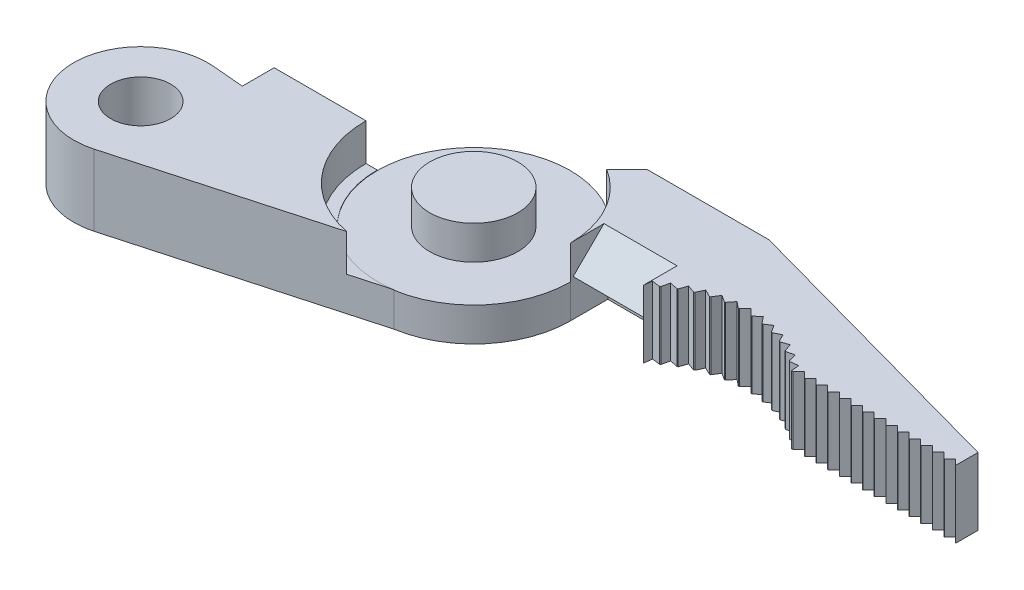
SolidWorks part; units mm, degrees
material "Plain Carbon Steel"
ref_plane "Front Plane" through (0, 0, 0) normal (0, 0, 1) x (1, 0, 0)
ref_plane "Top Plane" through (0, 0, 0) normal (0, 1, 0) x (1, 0, 0)
ref_plane "Right Plane" through (0, 0, 0) normal (1, 0, 0) x (0, 0, -1)
sketch "Sketch1" plane through (0, 0, 0) normal (0, 1, 0) x (1, 0, 0)
  circle A0 centre (0, 0) radius 6.5405
  circle A1 centre (0, 0) radius 2.9845
  dimension "D1" = 13.081
  dimension "D2" = 5.969
extrude "Boss-Extrude1" add sketch "Sketch1" along normal blind 4.826
sketch "Sketch2" plane through (0, 0, 0) normal (0, 1, 0) x (1, 0, 0)
  line L0 (-6.5405, 0) -> (-13.5255, 0)
  line L1 (-13.5255, 0) -> (-13.5255, -2.159)
  line L2 (-15.6763, -1.9708) -> (-13.5255, -2.159)
  line L3 (1.0584, -6.4543) -> (-14.8567, -10.8736)
  circle A1 centre (-16.0722, -6.4964) radius 2.032
  circle A2 centre (0, 0) radius 2.9845 construction
  arc A3 (-15.6763, -1.9708) -> (-14.8567, -10.8736) centre (-16.0722, -6.4964) ccw
  arc A4 (-6.5405, 0) -> (1.0584, -6.4543) centre (0, 0) ccw
  dimension "D1" = 4.064
  dimension "D6" = 17.3355
  dimension "D7" = 1.0584
  dimension "D3" = 4.5429
  dimension "D4" = 6.5405
  dimension "D2" = 6.985
  dimension "D5" = 85
extrude "Boss-Extrude2" add sketch "Sketch2" along normal up to surface (4.826 mm away) up to face at (0, 4.826, 6.5405)
hole_wizard "#42 (0.0935) Diameter Hole1" positions "Sketch6" profile "Sketch7" hole size "#42" standard "ANSI Inch"
sketch "Sketch6" plane through (0, 0, 0) normal (0, 0, -1) x (-1, 0, 0)
  line L0 (13.5255, 4.826) -> (13.5255, 0) construction
  line L1 (6.5405, 0) -> (13.5255, 0) construction
  point P0 (10.033, 2.413)
  dimension "D1" = 3.4925
  dimension "D2" = 2.413
sketch "Sketch7" plane through (-10.033, 2.413, 0) normal (1, 0, 0) x (0, 1, 0)
  line L0 (0, 0) -> (0, 2.7455)
  line L1 (0, 2.7455) -> (1.1874, 2.032)
  line L2 (1.1874, 2.032) -> (1.1874, 0)
  line L5 (1.1874, 0) -> (0, 0)
  line L10 (0, 2.7455) -> (-1.1875, 2.032) construction
  line L11 (0, -6.35) -> (0, 107.95) construction
  dimension "Hole Dia." = 2.3749
  dimension "Hole Depth" = 2.032
  dimension "Drill Angle" = 118
sketch "Sketch8" plane through (0, 0, 0) normal (0, 1, 0) x (1, 0, 0)
  line L0 (13.081, 6.9215) -> (32.639, 1.524)
  line L1 (32.639, 1.524) -> (32.639, 0)
  line L2 (32.639, 0) -> (21.5265, 0)
  line L3 (13.081, 6.9215) -> (4.826, 6.9215)
  line L4 (4.826, 6.9215) -> (3.4568, 5.5523)
  line L5 (6.5405, 0) -> (11.4935, 0)
  arc A2 (1.0584, -6.4543) -> (-6.5405, 0) centre (0, 0) ccw construction
  arc A4 (21.5265, 0) -> (11.4935, 0) centre (16.51, -5.7358) ccw
  arc A5 (6.5405, 0) -> (3.4568, 5.5523) centre (0, 0) ccw
  dimension "D1" = 0.381
  dimension "D8" = 7.62
  dimension "D2" = 1.524
  dimension "D3" = 8.255
  dimension "D4" = 32.639
  dimension "D5" = 225
  dimension "D6" = 11.1125
  dimension "D7" = 4.953
  dimension "D9" = 4.826
extrude "Boss-Extrude3" add sketch "Sketch8" along normal up to surface (4.826 mm away) up to face at (-10.2367, 4.826, 2.2894)
sketch "Sketch9" plane through (0, 4.826, 0) normal (0, 1, 0) x (1, 0, 0)
  line L10 (-7.3025, 0) -> (-6.5405, 0)
  line L11 (-1.463, -7.1544) -> (1.0584, -6.4543)
  line L12 (-14.8567, -10.8736) -> (1.0584, -6.4543) construction
  line L32 (33.401, -0.762) -> (33.401, 2.1048)
  arc A4 (-7.3025, 0) -> (-1.463, -7.1544) centre (0, 0) ccw
  arc A5 (-6.5405, 0) -> (1.0584, -6.4543) centre (0, 0) ccw
  arc A6 (3.4568, 5.5523) -> (-6.5405, 0) centre (0, 0) ccw construction
  arc A7 (1.0584, -6.4543) -> (6.5405, 0) centre (0, 0) ccw construction
  line M26 (-6.5405, 0) -> (-13.5255, 0)
  line M30 (-14.8567, -10.8736) -> (1.0584, -6.4543)
  dimension "D1" = 7.3025
  dimension "D2" = 6.5405
  dimension "D3" = 2.6168
extrude "Cut-Extrude1" cut sketch "Sketch9" against normal blind 2.5082 contours A5 A4 M26 M30 region at (-6.9215, 4.826, 0.11)
sketch "Sketch10" plane through (0, 4.826, 0) normal (0, 1, 0) x (1, 0, 0)
  line L0 (32.639, 0) -> (32.258, 0.381)
  line L1 (32.258, 0.381) -> (31.877, 0)
  line L3 (21.5265, 0) -> (32.639, 0) construction
  line L4 (31.877, 0) -> (32.639, 0)
  dimension "D1" = 0.381
extrude "Cut-Extrude2" cut sketch "Sketch10" against normal through all
pattern_linear "LPattern1" count 14 spacing 0.7874 along (-1, 0, 0) of "Cut-Extrude2"
sketch "Sketch11" plane through (0, 4.826, 0) normal (0, 1, 0) x (1, 0, 0)
  line L0 (21.5265, 0) -> (21.4646, 0.5466)
  line L1 (21.4646, 0.5466) -> (20.9187, 0.4794)
  arc A0 (21.5265, 0) -> (11.4935, 0) centre (16.51, -5.7358) ccw construction
  arc A1 (21.5265, 0) -> (20.9187, 0.4794) centre (16.51, -5.7358) ccw
  dimension "D1" = 8.001
extrude "Cut-Extrude3" cut sketch "Sketch11" against normal through all
pattern_circular "CirPattern1" count 13 over 76.5 about axis through (16.51, 4.826, 5.7358) along (0, -1, 0) of "Cut-Extrude3" reverse direction yes
sketch "Sketch13" plane through (0, 4.826, 0) normal (0, 1, 0) x (1, 0, 0)
  line L0 (11.4935, 0) -> (11.4935, 2.54)
  line L1 (11.4935, 2.54) -> (6.5405, 2.54)
  line L2 (6.5405, 2.54) -> (6.5405, 0)
  line L3 (6.5405, 0) -> (11.4935, 0)
  dimension "D1" = 2.54
extrude "Cut-Extrude5" cut sketch "Sketch13" against normal blind 2.5082
sketch "Sketch14" plane through (6.5405, 0, 0) normal (1, 0, 0) x (0, 0, -1)
  line L0 (0, 2.3178) -> (2.54, 4.826)
  line L1 (2.54, 4.826) -> (2.54, 2.3177)
  line L2 (2.54, 2.3177) -> (2.54, 4.826) construction
  line L3 (2.54, 2.3177) -> (0, 2.3178) construction
  line L4 (2.54, 2.3177) -> (0, 2.3178)
extrude "Boss-Extrude4" add sketch "Sketch14" along normal up to next
sketch "Sketch15" plane through (0, 0, 0) normal (0, -1, 0) x (1, 0, 0)
  line L0 (6.5405, 0) -> (6.5405, -2.54)
  line L1 (6.5405, 0) -> (11.4935, 0) construction
  line L2 (6.5405, -2.54) -> (11.4935, -2.54)
  line L3 (11.4935, -2.54) -> (11.4935, 0)
  line L4 (11.4935, 0) -> (6.5405, 0)
  arc A0 (6.5405, 0) -> (1.0584, 6.4543) centre (0, 0) ccw construction
  dimension "D1" = 2.54
extrude "Cut-Extrude6" cut sketch "Sketch15" against normal blind 2.5082
sketch "Sketch16" plane through (0, 4.826, 0) normal (0, 1, 0) x (1, 0, 0)
  circle A0 centre (0, 0) radius 6.5405
extrude "Cut-Extrude7" cut sketch "Sketch16" against normal blind 2.54
sketch "Sketch18" plane through (0, 0, 0) normal (0, 1, 0) x (1, 0, 0)
  circle A0 centre (0, 0) radius 2.9845
  dimension "D1" = 5.969
extrude "Boss-Extrude5" add sketch "Sketch18" along normal blind 4.572
sketch "Sketch19" plane through (0, 4.826, 0) normal (0, 1, 0) x (1, 0, 0)
  line L76 (6.5405, 0) -> (6.5405, 2.54)
  line L77 (6.5405, 2.54) -> (11.4935, 2.54)
  line L78 (11.4935, 2.54) -> (11.4935, 0)
  line L79 (11.4935, 0) -> (11.4958, 0.002)
  line L80 (11.4958, 0.002) -> (11.5579, 0.5485)
  line L81 (11.5579, 0.5485) -> (12.1038, 0.4811)
  line L82 (12.1639, 0.5233) -> (12.2863, 1.0595)
  line L83 (12.2863, 1.0595) -> (12.8213, 0.9319)
  line L84 (12.8857, 0.9671) -> (13.0669, 1.4865)
  line L85 (13.0669, 1.4865) -> (13.5845, 1.3003)
  line L86 (13.6524, 1.3281) -> (13.8901, 1.8241)
  line L87 (13.8901, 1.8241) -> (14.3838, 1.5816)
  line L88 (14.4544, 1.6017) -> (14.7457, 2.0683)
  line L89 (14.7457, 2.0683) -> (15.2095, 1.7724)
  line L90 (15.2818, 1.7846) -> (15.6232, 2.2159)
  line L91 (15.6232, 2.2159) -> (16.0512, 1.8704)
  line L92 (16.1244, 1.8745) -> (16.5116, 2.2652)
  line L93 (16.5116, 2.2652) -> (16.8986, 1.8743)
  line L94 (16.9718, 1.8702) -> (17.4, 2.2156)
  line L95 (17.4, 2.2156) -> (17.7411, 1.7841)
  line L96 (17.8135, 1.7719) -> (18.2773, 2.0676)
  line L97 (18.2773, 2.0676) -> (18.5685, 1.6009)
  line L98 (18.6391, 1.5807) -> (19.1329, 1.8231)
  line L99 (19.1329, 1.8231) -> (19.3704, 1.327)
  line L100 (19.4383, 1.2991) -> (19.9559, 1.4851)
  line L101 (19.9559, 1.4851) -> (20.1369, 0.9657)
  line L102 (20.2013, 0.9305) -> (20.7364, 1.0579)
  line L103 (20.7364, 1.0579) -> (20.8586, 0.5215)
  line L104 (20.9187, 0.4794) -> (21.4646, 0.5466)
  line L105 (21.4646, 0.5466) -> (21.5265, 0)
  line L106 (21.5265, 0) -> (21.6408, 0)
  line L107 (21.6408, 0) -> (22.0218, 0.381)
  line L108 (22.0218, 0.381) -> (22.4028, 0)
  line L109 (22.4028, 0) -> (22.4282, 0)
  line L110 (22.4282, 0) -> (22.8092, 0.381)
  line L111 (22.8092, 0.381) -> (23.1902, 0)
  line L112 (23.1902, 0) -> (23.2156, 0)
  line L113 (23.2156, 0) -> (23.5966, 0.381)
  line L114 (23.5966, 0.381) -> (23.9776, 0)
  line L115 (23.9776, 0) -> (24.003, 0)
  line L116 (24.003, 0) -> (24.384, 0.381)
  line L117 (24.384, 0.381) -> (24.765, 0)
  line L118 (24.765, 0) -> (24.7904, 0)
  line L119 (24.7904, 0) -> (25.1714, 0.381)
  line L120 (25.1714, 0.381) -> (25.5524, 0)
  line L121 (25.5524, 0) -> (25.5778, 0)
  line L122 (25.5778, 0) -> (25.9588, 0.381)
  line L123 (25.9588, 0.381) -> (26.3398, 0)
  line L124 (26.3398, 0) -> (26.3652, 0)
  line L125 (26.3652, 0) -> (26.7462, 0.381)
  line L126 (26.7462, 0.381) -> (27.1272, 0)
  line L127 (27.1272, 0) -> (27.1526, 0)
  line L128 (27.1526, 0) -> (27.5336, 0.381)
  line L129 (27.5336, 0.381) -> (27.9146, 0)
  line L130 (27.9146, 0) -> (27.94, 0)
  line L131 (27.94, 0) -> (28.321, 0.381)
  line L132 (28.321, 0.381) -> (28.702, 0)
  line L133 (28.702, 0) -> (28.7274, 0)
  line L134 (28.7274, 0) -> (29.1084, 0.381)
  line L135 (29.1084, 0.381) -> (29.4894, 0)
  line L136 (29.4894, 0) -> (29.5148, 0)
  line L137 (29.5148, 0) -> (29.8958, 0.381)
  line L138 (29.8958, 0.381) -> (30.2768, 0)
  line L139 (30.2768, 0) -> (30.3022, 0)
  line L140 (30.3022, 0) -> (30.6832, 0.381)
  line L141 (30.6832, 0.381) -> (31.0642, 0)
  line L142 (31.0642, 0) -> (31.0896, 0)
  line L143 (31.0896, 0) -> (31.4706, 0.381)
  line L144 (31.4706, 0.381) -> (31.8516, 0)
  line L145 (31.8516, 0) -> (31.877, 0)
  line L146 (31.877, 0) -> (32.258, 0.381)
  line L147 (32.258, 0.381) -> (32.639, 0)
  line L148 (32.639, 0) -> (32.639, 1.524)
  line L149 (32.639, 1.524) -> (13.081, 6.9215)
  line L150 (13.081, 6.9215) -> (4.826, 6.9215)
  line L151 (4.826, 6.9215) -> (3.4568, 5.5523)
  line L152 (6.5405, 0) -> (6.5405, 2.54)
  line L153 (6.5405, 2.54) -> (11.4935, 2.54)
  line L154 (11.4935, 2.54) -> (11.4935, 0)
  line L155 (11.4935, 0) -> (11.4958, 0.002)
  line L156 (11.4958, 0.002) -> (11.5579, 0.5485)
  line L157 (11.5579, 0.5485) -> (12.1038, 0.4811)
  line L158 (12.1639, 0.5233) -> (12.2863, 1.0595)
  line L159 (12.2863, 1.0595) -> (12.8213, 0.9319)
  line L160 (12.8857, 0.9671) -> (13.0669, 1.4865)
  line L161 (13.0669, 1.4865) -> (13.5845, 1.3003)
  line L162 (13.6524, 1.3281) -> (13.8901, 1.8241)
  line L163 (13.8901, 1.8241) -> (14.3838, 1.5816)
  line L164 (14.4544, 1.6017) -> (14.7457, 2.0683)
  line L165 (14.7457, 2.0683) -> (15.2095, 1.7724)
  line L166 (15.2818, 1.7846) -> (15.6232, 2.2159)
  line L167 (15.6232, 2.2159) -> (16.0512, 1.8704)
  line L168 (16.1244, 1.8745) -> (16.5116, 2.2652)
  line L169 (16.5116, 2.2652) -> (16.8986, 1.8743)
  line L170 (16.9718, 1.8702) -> (17.4, 2.2156)
  line L171 (17.4, 2.2156) -> (17.7411, 1.7841)
  line L172 (17.8135, 1.7719) -> (18.2773, 2.0676)
  line L173 (18.2773, 2.0676) -> (18.5685, 1.6009)
  line L174 (18.6391, 1.5807) -> (19.1329, 1.8231)
  line L175 (19.1329, 1.8231) -> (19.3704, 1.327)
  line L176 (19.4383, 1.2991) -> (19.9559, 1.4851)
  line L177 (19.9559, 1.4851) -> (20.1369, 0.9657)
  line L178 (20.2013, 0.9305) -> (20.7364, 1.0579)
  line L179 (20.7364, 1.0579) -> (20.8586, 0.5215)
  line L180 (20.9187, 0.4794) -> (21.4646, 0.5466)
  line L181 (21.4646, 0.5466) -> (21.5265, 0)
  line L182 (21.5265, 0) -> (21.6408, 0)
  line L183 (21.6408, 0) -> (22.0218, 0.381)
  line L184 (22.0218, 0.381) -> (22.4028, 0)
  line L185 (22.4028, 0) -> (22.4282, 0)
  line L186 (22.4282, 0) -> (22.8092, 0.381)
  line L187 (22.8092, 0.381) -> (23.1902, 0)
  line L188 (23.1902, 0) -> (23.2156, 0)
  line L189 (23.2156, 0) -> (23.5966, 0.381)
  line L190 (23.5966, 0.381) -> (23.9776, 0)
  line L191 (23.9776, 0) -> (24.003, 0)
  line L192 (24.003, 0) -> (24.384, 0.381)
  line L193 (24.384, 0.381) -> (24.765, 0)
  line L194 (24.765, 0) -> (24.7904, 0)
  line L195 (24.7904, 0) -> (25.1714, 0.381)
  line L196 (25.1714, 0.381) -> (25.5524, 0)
  line L197 (25.5524, 0) -> (25.5778, 0)
  line L198 (25.5778, 0) -> (25.9588, 0.381)
  line L199 (25.9588, 0.381) -> (26.3398, 0)
  line L200 (26.3398, 0) -> (26.3652, 0)
  line L201 (26.3652, 0) -> (26.7462, 0.381)
  line L202 (26.7462, 0.381) -> (27.1272, 0)
  line L203 (27.1272, 0) -> (27.1526, 0)
  line L204 (27.1526, 0) -> (27.5336, 0.381)
  line L205 (27.5336, 0.381) -> (27.9146, 0)
  line L206 (27.9146, 0) -> (27.94, 0)
  line L207 (27.94, 0) -> (28.321, 0.381)
  line L208 (28.321, 0.381) -> (28.702, 0)
  line L209 (28.702, 0) -> (28.7274, 0)
  line L210 (28.7274, 0) -> (29.1084, 0.381)
  line L211 (29.1084, 0.381) -> (29.4894, 0)
  line L212 (29.4894, 0) -> (29.5148, 0)
  line L213 (29.5148, 0) -> (29.8958, 0.381)
  line L214 (29.8958, 0.381) -> (30.2768, 0)
  line L215 (30.2768, 0) -> (30.3022, 0)
  line L216 (30.3022, 0) -> (30.6832, 0.381)
  line L217 (30.6832, 0.381) -> (31.0642, 0)
  line L218 (31.0642, 0) -> (31.0896, 0)
  line L219 (31.0896, 0) -> (31.4706, 0.381)
  line L220 (31.4706, 0.381) -> (31.8516, 0)
  line L221 (31.8516, 0) -> (31.877, 0)
  line L222 (31.877, 0) -> (32.258, 0.381)
  line L223 (32.258, 0.381) -> (32.639, 0)
  line L224 (32.639, 0) -> (32.639, 1.524)
  line L225 (32.639, 1.524) -> (13.081, 6.9215)
  line L226 (13.081, 6.9215) -> (4.826, 6.9215)
  line L227 (4.826, 6.9215) -> (3.4568, 5.5523)
  arc A13 (6.5405, 0) -> (3.4568, 5.5523) centre (0, 0) ccw
  arc A14 (12.1639, 0.5233) -> (12.1038, 0.4811) centre (16.51, -5.7358) ccw
  arc A15 (12.8857, 0.9671) -> (12.8213, 0.9319) centre (16.51, -5.7358) ccw
  arc A16 (13.6524, 1.3281) -> (13.5845, 1.3003) centre (16.51, -5.7358) ccw
  arc A17 (14.4544, 1.6017) -> (14.3838, 1.5816) centre (16.51, -5.7358) ccw
  arc A18 (15.2818, 1.7846) -> (15.2095, 1.7724) centre (16.51, -5.7358) ccw
  arc A19 (16.1244, 1.8745) -> (16.0512, 1.8704) centre (16.51, -5.7358) ccw
  arc A20 (16.9718, 1.8702) -> (16.8986, 1.8743) centre (16.51, -5.7358) ccw
  arc A21 (17.8135, 1.7719) -> (17.7411, 1.7841) centre (16.51, -5.7358) ccw
  arc A22 (18.6391, 1.5807) -> (18.5685, 1.6009) centre (16.51, -5.7358) ccw
  arc A23 (19.4383, 1.2991) -> (19.3704, 1.327) centre (16.51, -5.7358) ccw
  arc A24 (20.2013, 0.9305) -> (20.1369, 0.9657) centre (16.51, -5.7358) ccw
  arc A25 (20.9187, 0.4794) -> (20.8586, 0.5215) centre (16.51, -5.7358) ccw
  arc A26 (6.5405, 0) -> (3.4568, 5.5523) centre (0, 0) ccw
  arc A27 (12.1639, 0.5233) -> (12.1038, 0.4811) centre (16.51, -5.7358) ccw
  arc A28 (12.8857, 0.9671) -> (12.8213, 0.9319) centre (16.51, -5.7358) ccw
  arc A29 (13.6524, 1.3281) -> (13.5845, 1.3003) centre (16.51, -5.7358) ccw
  arc A30 (14.4544, 1.6017) -> (14.3838, 1.5816) centre (16.51, -5.7358) ccw
  arc A31 (15.2818, 1.7846) -> (15.2095, 1.7724) centre (16.51, -5.7358) ccw
  arc A32 (16.1244, 1.8745) -> (16.0512, 1.8704) centre (16.51, -5.7358) ccw
  arc A33 (16.9718, 1.8702) -> (16.8986, 1.8743) centre (16.51, -5.7358) ccw
  arc A34 (17.8135, 1.7719) -> (17.7411, 1.7841) centre (16.51, -5.7358) ccw
  arc A35 (18.6391, 1.5807) -> (18.5685, 1.6009) centre (16.51, -5.7358) ccw
  arc A36 (19.4383, 1.2991) -> (19.3704, 1.327) centre (16.51, -5.7358) ccw
  arc A37 (20.2013, 0.9305) -> (20.1369, 0.9657) centre (16.51, -5.7358) ccw
  arc A38 (20.9187, 0.4794) -> (20.8586, 0.5215) centre (16.51, -5.7358) ccw
  dimension "D1" = 0
extrude "Cut-Extrude8" cut sketch "Sketch19" against normal blind 0.254
sketch "Sketch20" plane through (11.4935, 0, 0) normal (1, 0, 0) x (0, 0, -1)
  line L0 (2.54, 4.826) -> (2.2828, 4.572)
  line L1 (2.2828, 4.572) -> (2.54, 4.572)
  line L2 (2.54, 4.572) -> (2.54, 4.826)
extrude "Cut-Extrude9" cut sketch "Sketch20" against normal up to next
